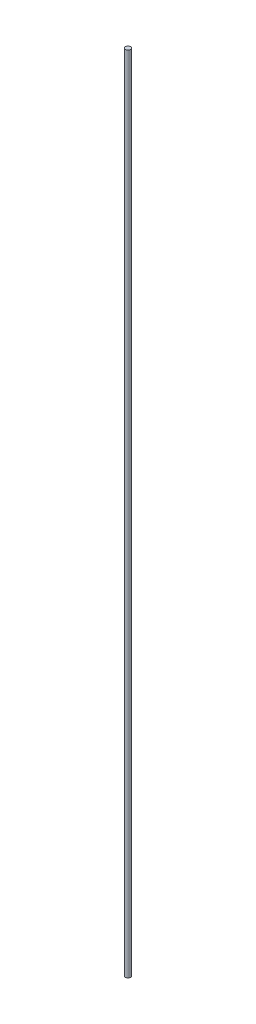
SolidWorks part; units mm, degrees
ref_plane "Front Plane" through (0, 0, 0) normal (0, 0, 1) x (1, 0, 0)
ref_plane "Top Plane" through (0, 0, 0) normal (0, 1, 0) x (1, 0, 0)
ref_plane "Right Plane" through (0, 0, 0) normal (1, 0, 0) x (0, 0, -1)
sketch "Sketch1" plane through (0, 0, 0) normal (0, 0, 1) x (1, 0, 0)
  line L0 (0, 0) -> (0, 2003.806)
  dimension "Length from Tank Model" = 2003.806
sweep "Sweep1" add path "Sketch1" circular profile diameter 12.7 parameters "D3"=12.7
equation "\"rebar diameter\"= .5"
equation "\"D3@Sweep1\"=\"rebar diameter\""
